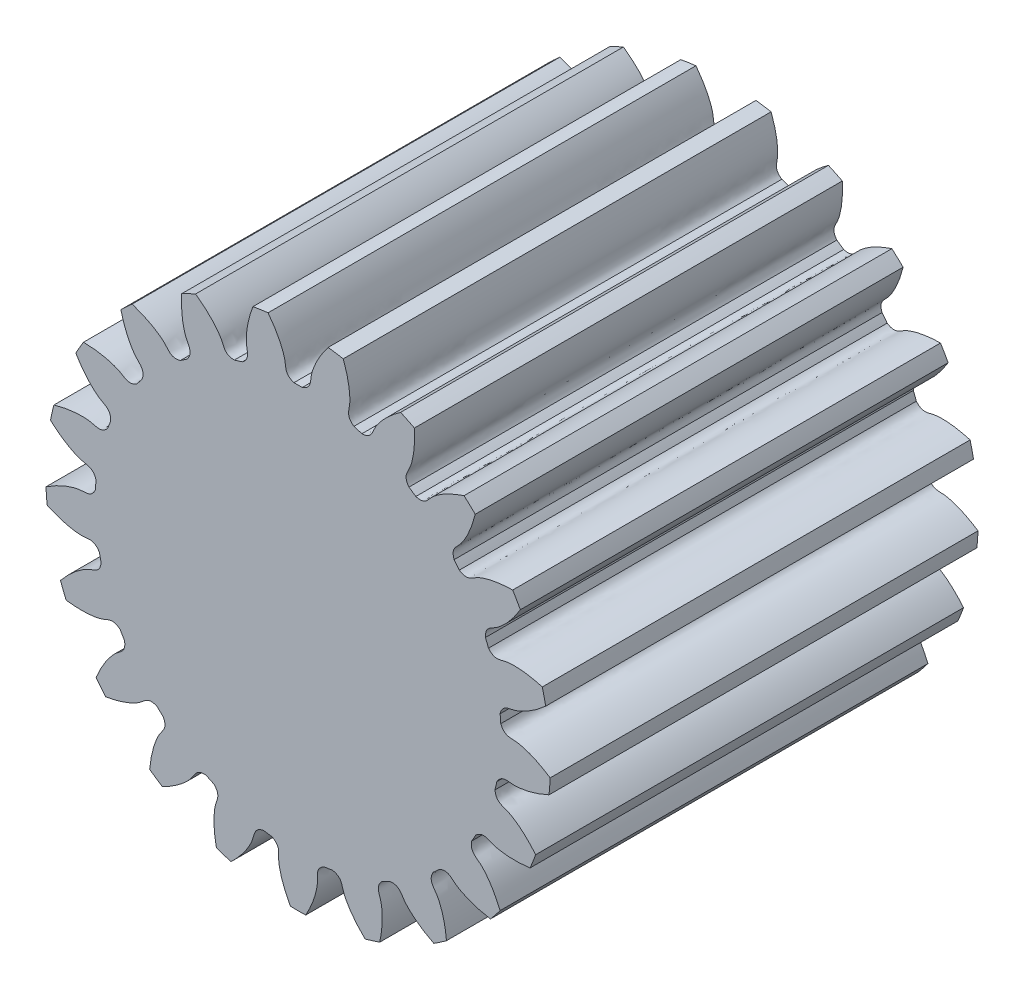
SolidWorks part; units mm, degrees
ref_plane "前视基准面" through (0, 0, 0) normal (0, 0, 1) x (1, 0, 0)
ref_plane "上视基准面" through (0, 0, 0) normal (0, 1, 0) x (1, 0, 0)
ref_plane "右视基准面" through (0, 0, 0) normal (1, 0, 0) x (0, 0, -1)
sketch "草图1" plane through (0, 0, 0) normal (0, 0, 1) x (1, 0, 0)
  circle A0 centre (0, 0) radius 11.5
extrude "凸台-拉伸1" add sketch "草图1" along normal blind 30
ref_axis "基准轴1" through (0, 0, -1.5) along (0, 0, 1)
sketch "草图2" plane through (0, 0, 0) normal (0, 0, 1) x (1, 0, 0)
  line L0 (0, 0) -> (0, 11.5) construction
  circle A0 centre (0, 0) radius 11.5 construction
  arc A1 (0.1897, 9.2481) -> (-0.1897, 9.2481) centre (0, 0) ccw
  arc A2 (3.1375, 13.0349) -> (-3.1375, 13.0349) centre (0, 0) ccw
  spline S0 degree 3 poles (0.1897, 9.2481) (0.5993, 9.3851) (0.5528, 9.6695) (0.6062, 9.9459) (0.6124, 9.9748) (0.6201, 10.0075) (0.6294, 10.0438) (0.6405, 10.0837) (0.6535, 10.1272) (0.6685, 10.1742) (0.6858, 10.2246) (0.7054, 10.2783) (0.7276, 10.3354) (0.7524, 10.3956) (0.7799, 10.4589) (0.8104, 10.5253) (0.8439, 10.5946) (0.8805, 10.6667) (0.9205, 10.7416) (0.9638, 10.8191) (1.0107, 10.8991) (1.0613, 10.9815) (1.1156, 11.0663) (1.1738, 11.1532) (1.236, 11.2421) (1.3023, 11.333) (1.3728, 11.4257) (1.4475, 11.52) (1.5267, 11.6159) (1.6103, 11.7132) (1.6985, 11.8117) (1.7913, 11.9113) (1.8889, 12.0119) (1.9912, 12.1133) (2.0984, 12.2153) (2.2106, 12.3179) (2.3277, 12.4208) (2.4499, 12.5238) (2.5772, 12.6269) (2.7096, 12.7298) (2.8953, 12.8683) (3.0392, 12.969) (3.1375, 13.0349) knots 0 0 0 0 0.161235 0.166477 0.172526 0.179381 0.187043 0.195511 0.204786 0.214867 0.225755 0.237449 0.24995 0.263258 0.277371 0.292292 0.308019 0.324552 0.341892 0.360038 0.378991 0.39875 0.419316 0.440689 0.462868 0.485853 0.509645 0.534243 0.559648 0.58586 0.612878 0.640702 0.669333 0.69877 0.729014 0.760065 0.791922 0.824585 0.858055 0.892332 0.927415 1 1 1 1
  spline S1 degree 3 poles (-0.1897, 9.2481) (-0.5993, 9.3851) (-0.5528, 9.6695) (-0.6062, 9.9459) (-0.6124, 9.9748) (-0.6201, 10.0075) (-0.6294, 10.0438) (-0.6405, 10.0837) (-0.6535, 10.1272) (-0.6685, 10.1742) (-0.6858, 10.2246) (-0.7054, 10.2783) (-0.7276, 10.3354) (-0.7524, 10.3956) (-0.7799, 10.4589) (-0.8104, 10.5253) (-0.8439, 10.5946) (-0.8805, 10.6667) (-0.9205, 10.7416) (-0.9638, 10.8191) (-1.0107, 10.8991) (-1.0613, 10.9815) (-1.1156, 11.0663) (-1.1738, 11.1532) (-1.236, 11.2421) (-1.3023, 11.333) (-1.3728, 11.4257) (-1.4475, 11.52) (-1.5267, 11.6159) (-1.6103, 11.7132) (-1.6985, 11.8117) (-1.7913, 11.9113) (-1.8889, 12.0119) (-1.9912, 12.1133) (-2.0984, 12.2153) (-2.2106, 12.3179) (-2.3277, 12.4208) (-2.4499, 12.5238) (-2.5772, 12.6269) (-2.7096, 12.7298) (-2.8953, 12.8683) (-3.0392, 12.969) (-3.1375, 13.0349) knots 0 0 0 0 0.161235 0.166477 0.172526 0.179381 0.187043 0.195511 0.204786 0.214867 0.225755 0.237449 0.24995 0.263258 0.277371 0.292292 0.308019 0.324552 0.341892 0.360038 0.378991 0.39875 0.419316 0.440689 0.462868 0.485853 0.509645 0.534243 0.559648 0.58586 0.612878 0.640702 0.669333 0.69877 0.729014 0.760065 0.791922 0.824585 0.858055 0.892332 0.927415 1 1 1 1
extrude "切除-拉伸1" cut sketch "草图2" along normal through all
pattern_circular "阵列(圆周)1" count 21 every 17.143 about axis through (0, 0, -1.5) along (0, 0, 1) of "切除-拉伸1"
sketch "草图3" plane through (0, 0, 0) normal (0, 0, 1) x (1, 0, 0)
  circle A0 centre (0, 0) radius 10.5 construction
  dimension "Dn" = 21
sketch "草图4" plane through (0, 0, 30) normal (0, 0, 1) x (1, 0, 0)
  circle A0 centre (0, 0) radius 21.6531
extrude "切除-拉伸2" cut sketch "草图4" against normal offset from surface (10.5 mm away) 19.5 up to face at (0, 0, 0)
